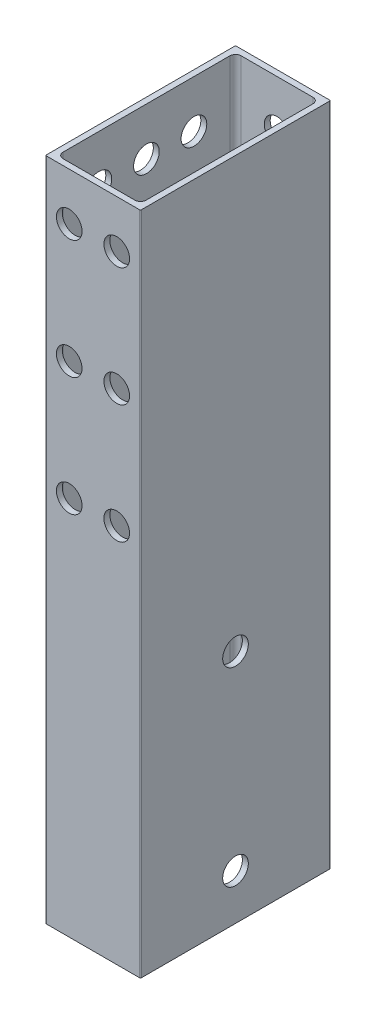
SolidWorks part; units mm, degrees
material "6061-T6 (SS)"
ref_plane "Front Plane" through (0, 0, 0) normal (0, 0, 1) x (1, 0, 0)
ref_plane "Top Plane" through (0, 0, 0) normal (0, 1, 0) x (1, 0, 0)
ref_plane "Right Plane" through (0, 0, 0) normal (1, 0, 0) x (0, 0, -1)
sketch "Sketch1" plane through (0, 0, 0) normal (0, 1, 0) x (1, 0, 0)
  line L0 (0.254, 50.8) -> (25.146, 50.8)
  line L1 (25.4, 50.546) -> (25.4, 0.254)
  line L2 (25.146, 0) -> (0.254, 0)
  line L3 (0, 0.254) -> (0, 50.546)
  line L4 (1.5875, 3.1115) -> (1.5875, 47.6885)
  line L5 (3.1115, 49.2125) -> (22.2885, 49.2125)
  line L6 (23.8125, 47.6885) -> (23.8125, 3.1115)
  line L7 (22.2885, 1.5875) -> (3.1115, 1.5875)
  line L8 (1.5875, 0.254) -> (1.5875, 50.546) construction
  line L9 (0.254, 49.2125) -> (25.146, 49.2125) construction
  line L10 (23.8125, 50.546) -> (23.8125, 0.254) construction
  line L11 (25.146, 1.5875) -> (0.254, 1.5875) construction
  arc A0 (0.254, 0) -> (0, 0.254) centre (0.254, 0.254) cw
  arc A1 (25.4, 0.254) -> (25.146, 0) centre (25.146, 0.254) cw
  arc A2 (25.146, 50.8) -> (25.4, 50.546) centre (25.146, 50.546) cw
  arc A3 (0.254, 50.8) -> (0, 50.546) centre (0.254, 50.546) ccw
  arc A4 (1.5875, 3.1115) -> (3.1115, 1.5875) centre (3.1115, 3.1115) ccw
  arc A5 (22.2885, 1.5875) -> (23.8125, 3.1115) centre (22.2885, 3.1115) ccw
  arc A6 (23.8125, 47.6885) -> (22.2885, 49.2125) centre (22.2885, 47.6885) ccw
  arc A7 (1.5875, 47.6885) -> (3.1115, 49.2125) centre (3.1115, 47.6885) cw
  point P8 (0, 0)
  point P11 (25.4, 0)
  point P14 (25.4, 50.8)
  point P17 (0, 50.8)
  dimension "D3" = 0.254
  dimension "D5" = 1.524
  dimension "D1" = 25.4
  dimension "D2" = 50.8
  dimension "D4" = 1.5875
extrude "Boss-Extrude1" add sketch "Sketch1" along normal blind 177.8
sketch "Sketch2" plane through (0, 0, 0) normal (-1, 0, 0) x (0, 0, 1)
  line L0 (-25.4, 0) -> (-25.4, 177.8) construction
  line L1 (-50.546, 0) -> (-0.254, 0) construction
  line L2 (-50.546, 177.8) -> (-0.254, 177.8) construction
  line L3 (-50.546, 177.8) -> (-50.546, 0) construction
  circle A0 centre (-25.4, 12.192) radius 10.16
  circle A1 centre (-25.4, 12.192) radius 3.429
  circle A2 centre (-25.4, 62.992) radius 10.16
  circle A3 centre (-25.4, 62.992) radius 3.429
  circle A4 centre (-38.1, 165.1) radius 3.429
  circle A5 centre (-25.4, 165.1) radius 3.429
  circle A6 centre (-12.7, 165.1) radius 3.429
  circle A7 centre (-25.4, 133.35) radius 3.429
  circle A8 centre (-12.7, 133.35) radius 3.429
  circle A9 centre (-25.4, 101.6) radius 3.429
  circle A10 centre (-12.7, 101.6) radius 3.429
  circle A11 centre (-38.1, 133.35) radius 3.429
  circle A12 centre (-38.1, 101.6) radius 3.429
  dimension "D1" = 20.32
  dimension "D2" = 6.858
  dimension "D6" = 12.446
  dimension "D3" = 12.192
  dimension "D5" = 50.8
  dimension "D7" = 12.7
  dimension "D10" = 31.75
  dimension "D11" = 12.7
  dimension "D4" = 2
  dimension "D8" = 3
  dimension "D9" = 3
extrude "Cut-Extrude1" cut sketch "Sketch2" against normal blind 12.7
extrude "Cut-Extrude2" cut sketch "Sketch2<3>" against normal through all contours L0 A3 | A3 L0 | L0 A1 | A1 L0 region at (0, 12.192, -26.8553) region at (0, 12.192, -23.9447) region at (0, 62.992, -26.8553) region at (0, 62.992, -23.9447)
sketch "Sketch2<3>" plane through (0, 0, 0) normal (-1, 0, 0) x (0, 0, 1) same geometry as "Sketch2"
sketch "Sketch3" plane through (0, 0, 0) normal (0, 0, 1) x (1, 0, 0)
  line L0 (25.146, 177.8) -> (25.146, 0) construction
  line L1 (0.254, 177.8) -> (25.146, 177.8) construction
  circle A0 centre (19.05, 165.1) radius 3.429
  circle A1 centre (6.35, 165.1) radius 3.429
  circle A2 centre (6.35, 133.35) radius 3.429
  circle A3 centre (6.35, 101.6) radius 3.429
  circle A4 centre (19.05, 133.35) radius 3.429
  circle A5 centre (19.05, 101.6) radius 3.429
  dimension "D1" = 6.858
  dimension "D2" = 6.096
  dimension "D3" = 12.7
  dimension "D6" = 12.7
  dimension "D7" = 31.75
  dimension "D4" = 2
  dimension "D5" = 3
extrude "Cut-Extrude3" cut sketch "Sketch3" against normal blind 2.54
sketch "Sketch4" plane through (0, 0, -50.8) normal (0, 0, -1) x (-1, 0, 0)
  line L0 (-12.7, 177.8) -> (-12.7, 101.6) construction
  line L1 (-25.146, 177.8) -> (-0.254, 177.8) construction
  circle A0 centre (-12.7, 165.1) radius 3.429
  circle A1 centre (-12.7, 139.7) radius 3.429
  circle A2 centre (-12.7, 127) radius 3.429
  circle A3 centre (-12.7, 101.6) radius 3.429
  point P12 (-12.7, 100.6215)
  dimension "D1" = 6.858
  dimension "D2" = 12.7
  dimension "D3" = 25.4
  dimension "D4" = 12.7
  dimension "D5" = 25.4
extrude "Cut-Extrude4" cut sketch "Sketch4" against normal blind 2.54
